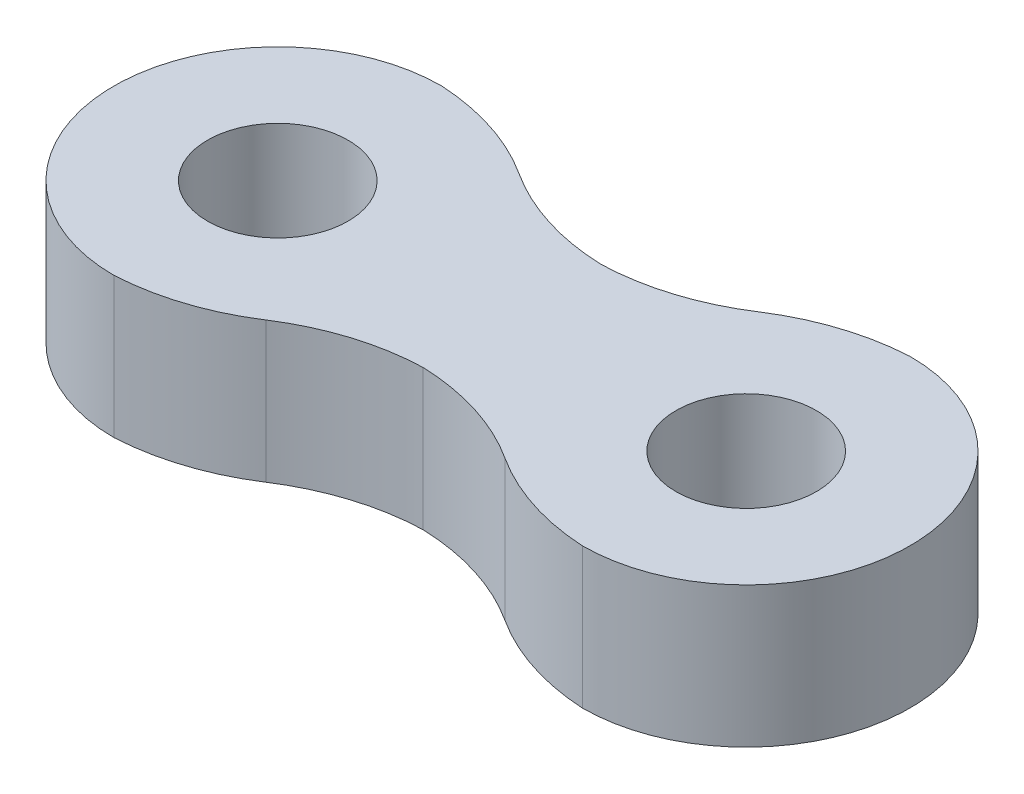
SolidWorks part; units mm, degrees
material "Acrylic (Medium-high impact)"
ref_plane "Plano frontal" through (0, 0, 0) normal (0, 0, 1) x (1, 0, 0)
ref_plane "Plano superior" through (0, 0, 0) normal (0, 1, 0) x (1, 0, 0)
ref_plane "Plano direito" through (0, 0, 0) normal (1, 0, 0) x (0, 0, -1)
sketch "Sketch1" plane through (0, 0, 0) normal (0, 1, 0) x (1, 0, 0)
  line L0 (-5, 0) -> (5, 0) construction
  line L1 (-5, 3.5) -> (5, 3.5)
  line L2 (-5, -3.5) -> (5, -3.5)
  arc A0 (-5, 3.5) -> (-5, -3.5) centre (-5, 0) ccw
  arc A1 (5, -3.5) -> (5, 3.5) centre (5, 0) ccw
  circle A2 centre (-5, 0) radius 1.5
  circle A3 centre (5, 0) radius 1.5
  point P2 (0, 0)
  dimension "D1" = 3
  dimension "D2" = 2
  dimension "D3" = 10
extrude "Boss-Extrude1" add sketch "Sketch1" along normal mid plane 3
sketch "Sketch2" plane through (0, 0, 0) normal (0, 1, 0) x (1, 0, 0)
  line L0 (-5, -3.5) -> (5, -3.5) construction
  line L1 (-3.5, -3.5) -> (3.5, -3.5)
  line L2 (-3.5, -3.5) -> (-3.5, -1.9)
  line L3 (-3.5, -1.9) -> (3.5, -1.9)
  line L4 (3.5, -3.5) -> (3.5, -1.9)
  line L5 (-1.65, 0) -> (1.65, 0) construction
  line L6 (3.5, 3.5) -> (3.5, 1.9)
  line L7 (-3.5, 1.9) -> (3.5, 1.9)
  line L8 (-3.5, 3.5) -> (-3.5, 1.9)
  line L9 (-3.5, 3.5) -> (3.5, 3.5)
  circle A0 centre (5, 0) radius 1.5 construction
  circle A1 centre (-5, 0) radius 1.5 construction
  dimension "D2" = 1.5
  dimension "D3" = 1.5
  dimension "D1" = 1.6
extrude "Cut-Extrude1" cut sketch "Sketch2" against normal through all both and the other way through all
fillet "Fillet1" radius 5 4 edges at (-3.5, 0, 1.9) (-3.5, 0, -1.9) (3.5, 0, 1.9) (3.5, 0, -1.9)
fillet "Fillet2" radius 5 4 edges at (-3.5, 0, 3.5) (-3.5, 0, -3.5) (3.5, 0, -3.5) (3.5, 0, 3.5)
